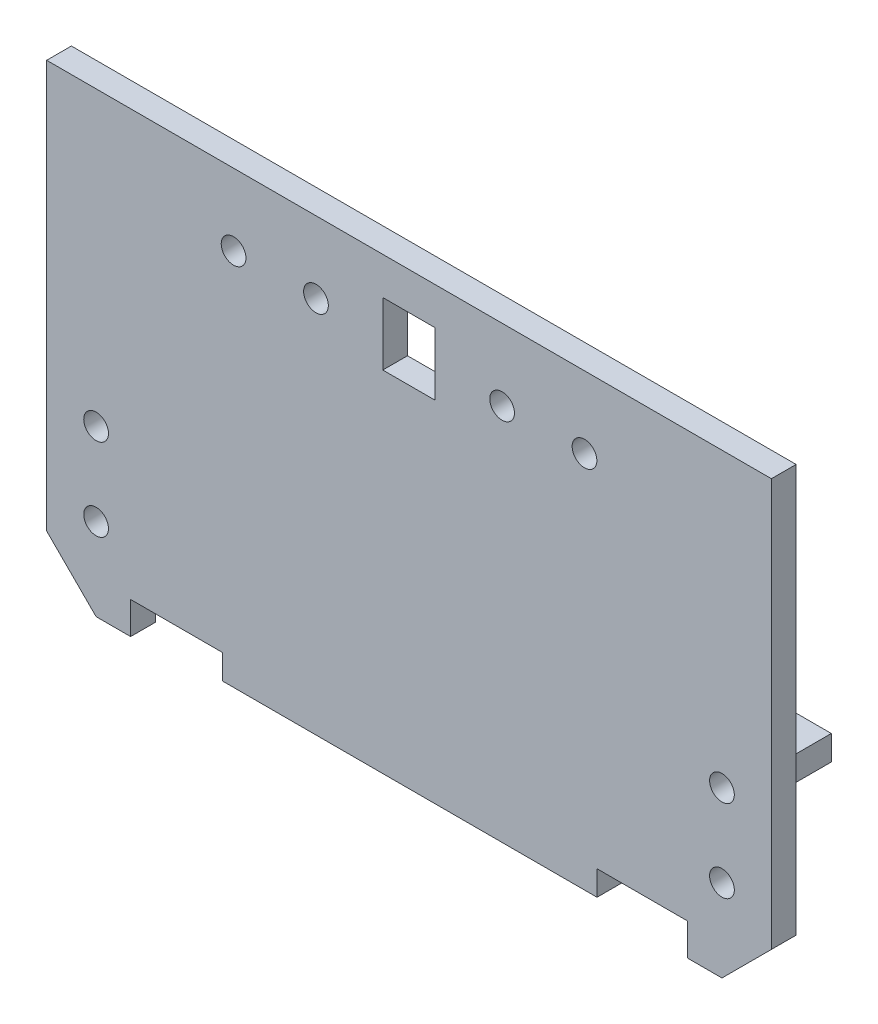
SolidWorks part; units mm, degrees
ref_plane "Front Plane" through (0, 0, 0) normal (0, 0, 1) x (1, 0, 0)
ref_plane "Top Plane" through (0, 0, 0) normal (0, 1, 0) x (1, 0, 0)
ref_plane "Right Plane" through (0, 0, 0) normal (1, 0, 0) x (0, 0, -1)
sketch "Sketch1" plane through (0, 0, 0) normal (0, 0, 1) x (1, 0, 0)
  line L1 (-33.7879, 25.3517) -> (-33.7879, 14.6993) construction
  line L2 (-33.7879, 14.6993) -> (-37.9759, 14.6993) construction
  line L3 (-37.9759, 14.6993) -> (-43.9759, 20.6993) construction
  line L4 (-43.9759, 20.6993) -> (-43.9759, 28.4551) construction
  line L7 (-33.7879, 18.6025) -> (-33.7879, 14.6993)
  line L8 (-33.7879, 14.6993) -> (-37.9759, 14.6993)
  line L9 (-37.9759, 14.6993) -> (-43.9759, 20.6993)
  line L10 (-43.9759, 20.6993) -> (-43.9759, 28.4551)
  line L11 (-43.9759, 28.4551) -> (-43.9759, 70.1751)
  line L14 (33.7879, 18.6025) -> (33.7879, 14.6993)
  line L15 (33.7879, 14.6993) -> (37.9759, 14.6993)
  line L16 (37.9759, 14.6993) -> (43.9759, 20.6993)
  line L17 (43.9759, 20.6993) -> (43.9759, 28.4551)
  line L18 (-43.9759, 70.1751) -> (43.9759, 70.1751)
  line L19 (33.7879, 18.6025) -> (-33.7879, 18.6025)
  line L21 (43.9759, 70.1751) -> (43.9759, 28.4551)
  dimension "D1" = 41.72
extrude "Boss-Extrude1" add sketch "Sketch1" along normal blind 3 contours L21 L17 L16 L15 L14 L19 L7 L8 L9 L10 L11 L18
sketch "Sketch2" plane through (0, 0, 3) normal (0, 0, 1) x (1, 0, 0)
  line L0 (37.9759, 14.6993) -> (37.9759, 24.6993) construction
  line L1 (0, 0) -> (0, 83.7503) construction
  line L3 (21.2938, 63.9782) -> (1.2938, 63.9782) construction
  line L4 (21.2938, 63.9782) -> (21.2938, 61.4782) construction
  circle A0 centre (37.9759, 24.6993) radius 1.5
  circle A2 centre (37.9759, 34.6993) radius 1.5
  circle A3 centre (-37.9759, 24.6993) radius 1.5
  circle A4 centre (-37.9759, 34.6993) radius 1.5
  circle A5 centre (21.2938, 61.4782) radius 1.5
  circle A6 centre (11.2938, 61.4782) radius 1.5
  circle A7 centre (-11.2938, 61.4782) radius 1.5
  circle A8 centre (-21.2938, 61.4782) radius 1.5
  dimension "D2" = 2
  dimension "D3" = 3
  dimension "D4" = 2.5
  dimension "D5" = 20
  dimension "D6" = 3
  dimension "D1" = 10
  dimension "D7" = 2
extrude "Cut-Extrude1" cut sketch "Sketch2" against normal up to surface (3 mm away) up to face at (0, 27.7751, 0)
sketch "Sketch3" plane through (0, 0, 0) normal (0, 0, -1) x (-1, 0, 0)
  line L0 (3.1837, 65.6365) -> (-3.1663, 65.6365)
  line L1 (-3.1663, 65.6365) -> (-3.1663, 58.0165)
  line L2 (-3.1663, 58.0165) -> (3.1837, 58.0165)
  line L3 (3.1837, 58.0165) -> (3.1837, 65.6365)
  dimension "D1" = 7.62
  dimension "D2" = 6.35
extrude "Cut-Extrude2" cut sketch "Sketch3" against normal up to surface (3 mm away) up to face at (22.7938, 61.4782, 3)
sketch "Sketch4" plane through (0, 18.6025, 0) normal (0, -1, 0) x (1, 0, 0)
  line L0 (-12.6851, -20.4341) -> (14.9476, -20.4341)
  line L1 (14.9476, -20.4341) -> (14.9476, -25.4341)
  line L2 (14.9476, -25.4341) -> (22.8153, -25.4341)
  line L3 (-22.6647, 3) -> (-22.6647, -25.4341)
  line L7 (22.8153, 3) -> (22.8153, -25.4341)
  line L12 (-12.6851, -25.4341) -> (-22.6647, -25.4341)
  line L14 (22.8153, 3) -> (-22.6647, 3)
  line L15 (-22.6647, 3) -> (22.8153, 3)
  line L19 (-12.6851, -20.4341) -> (-12.6851, -25.4341)
  line M12 (-33.7879, 0) -> (33.7879, 0)
  line M14 (33.7879, 3) -> (-33.7879, 3)
  dimension "D2" = 45.48
  dimension "D3" = 5
extrude "Boss-Extrude2" add sketch "Sketch4" along normal blind 3 contours L19 L7 L3 L12 M12 | L7 L3 M14 M12 region at (-0.068, 18.6025, -11.3312) region at (0.0753, 18.6025, 1.5)
